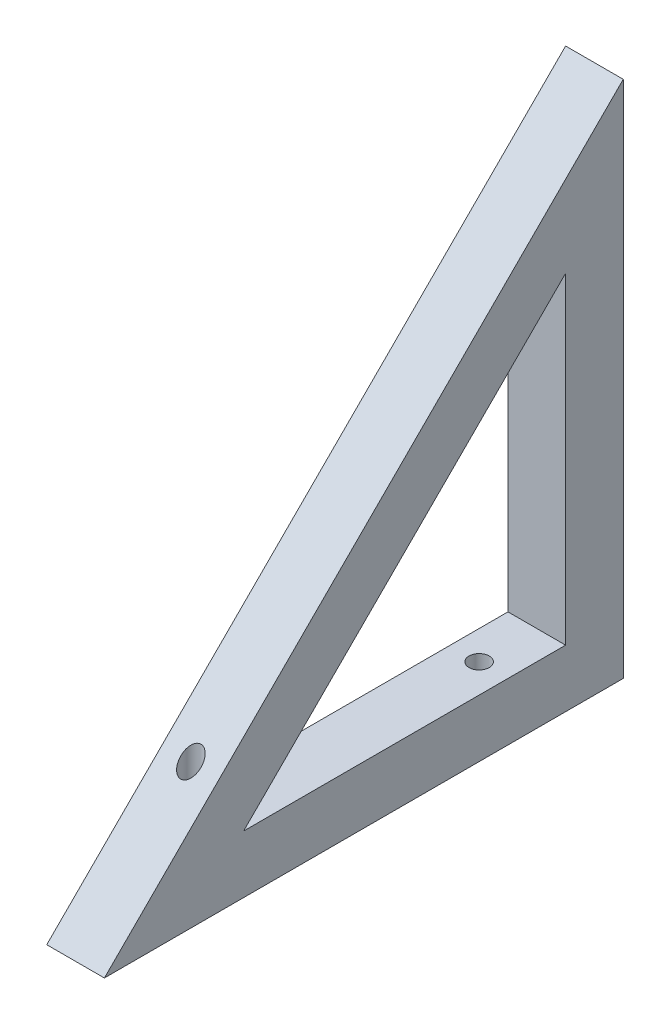
SolidWorks part; units mm, degrees
ref_plane "Front Plane" through (0, 0, 0) normal (0, 0, 1) x (1, 0, 0)
ref_plane "Top Plane" through (0, 0, 0) normal (0, 1, 0) x (1, 0, 0)
ref_plane "Right Plane" through (0, 0, 0) normal (1, 0, 0) x (0, 0, -1)
sketch "Sketch1" plane through (0, 0, 0) normal (1, 0, 0) x (0, 0, -1)
  line L0 (0, 0) -> (90, 0)
  line L1 (0, 0) -> (90, 90)
  line L2 (90, 90) -> (90, 0)
  line L3 (80, 65.8579) -> (80, 10)
  line L4 (24.1421, 10) -> (80, 10)
  line L5 (24.1421, 10) -> (80, 65.8579)
  dimension "D1" = 10
  dimension "D2" = 45
  dimension "D3" = 90
extrude "Boss-Extrude1" add sketch "Sketch1" along normal blind 10
sketch "Sketch2" plane through (0, 0, 0) normal (0, -1, 0) x (1, 0, 0)
  line L0 (5, 0) -> (5, -90) construction
  line L1 (10, 0) -> (0, 0) construction
  line L2 (10, -90) -> (0, -90) construction
  line L3 (10, -45) -> (0, -45) construction
  line L4 (10, 0) -> (10, -90) construction
  line L5 (0, 0) -> (0, -90) construction
  circle A0 centre (5, -20) radius 1.75
  circle A1 centre (5, -70) radius 1.75
  dimension "D1" = 3.5
  dimension "D2" = 25
extrude "Cut-Extrude1" cut sketch "Sketch2" against normal up to next
sketch "Sketch3" plane through (10, 0, 0) normal (1, 0, 0) x (0, 0, -1)
  line L0 (90, 0) -> (90, 90) construction
  line L1 (90, 45) -> (80, 45) construction
  line L2 (80, 10) -> (80, 65.8579) construction
  circle A0 centre (85, 45) radius 2.5
  dimension "D1" = 5
